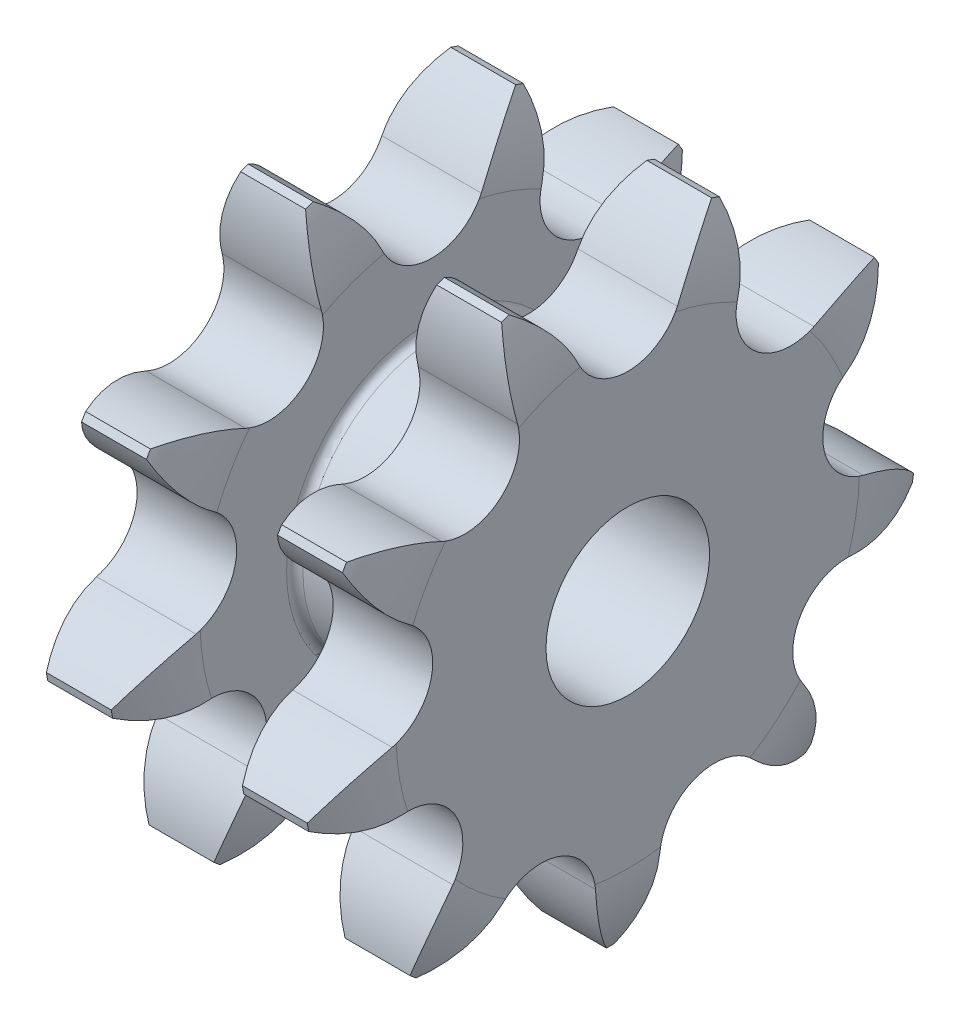
SolidWorks part; units mm, degrees
ref_plane "Plane1" through (0, 0, 0) normal (0, 0, 1) x (1, 0, 0)
ref_plane "Plane2" through (0, 0, 0) normal (0, 1, 0) x (1, 0, 0)
ref_plane "Plane3" through (0, 0, 0) normal (1, 0, 0) x (0, 0, -1)
sketch "Clipboard" plane through (0, 0, 0) normal (0, 1, 0) x (1, 0, 0)
  line L0 (0, 0) -> (12.5436, -1.9867)
  line L1 (-15, 0) -> (100, 0) construction
  line L2 (0, 0) -> (-0.8416, 0.9512)
  line L3 (0, 0) -> (-11.863, 4.5341)
  line L4 (0, 0) -> (3.0618, 0.4849)
  line L5 (0, 0) -> (-2.8109, -1.0484)
  line L6 (0, 0) -> (-17.9719, -12.1257)
  line L7 (-0.8416, 0.9512) -> (22.6002, 5.5078)
  line L8 (-76.2, 38.1) -> (-75.2, 38.1)
  line L9 (-73.4321, 41.7084) -> (-72.837, 41.7846)
  line L10 (-73.4741, 12.9512) -> (-59.0941, 12.9512)
  circle A0 centre (0, 0) radius 3.975
  circle A1 centre (0, 0) radius 10.0465
  circle A2 centre (0, 0) radius 25
  dimension "Num_teeth" = 9
  dimension "Thickness" = 21.68
  dimension "Fillet_rad" = 0.6
sketch "BasProSke" plane through (0, 0, 0) normal (0, 1, 0) x (1, 0, 0)
  line L0 (-10, 0) -> (60, 0) construction
  line L1 (0, 0) -> (0, 16.9929)
  line L2 (0, 0) -> (21.68, 0)
  line L3 (21.68, 0) -> (21.68, 16.9929)
  line L4 (20.41, 22.5287) -> (1.27, 22.5287)
  arc A0 (0, 16.9929) -> (1.27, 22.5287) centre (12.7, 16.9929) cw
  arc A1 (21.68, 16.9929) -> (20.41, 22.5287) centre (8.98, 16.9929) ccw
  dimension "D1" = 12.7
  dimension "Thickness" = 21.68
  dimension "Diameter" = 45.0573
  dimension "G1" = 1.27
revolve "Base-Revolve" add sketch "BasProSke" angle 360 about L0
sketch "GrvSke" plane through (0, 0, 0) normal (0, 1, 0) x (1, 0, 0)
  line L0 (7.3, 16.9929) -> (7.3, 10.6465)
  line L1 (7.9, 10.0465) -> (13.78, 10.0465)
  line L2 (14.38, 10.6465) -> (14.38, 16.9929)
  line L3 (6.03, 22.5287) -> (15.65, 22.5287)
  line L4 (10.84, 0) -> (10.84, 52.07) construction
  line L5 (-10, 0) -> (60, 0) construction
  line L6 (0, 0) -> (35.56, 0) construction
  arc A0 (14.38, 16.9929) -> (15.65, 22.5287) centre (27.08, 16.9929) cw
  arc A1 (7.3, 16.9929) -> (6.03, 22.5287) centre (-5.4, 16.9929) ccw
  arc A2 (7.3, 10.6465) -> (7.9, 10.0465) centre (7.9, 10.6465) ccw
  arc A3 (13.78, 10.0465) -> (14.38, 10.6465) centre (13.78, 10.6465) ccw
  dimension "D1" = 12.7
  dimension "Diameter" = 45.0573
  dimension "Fillet_rad" = 0.6
  dimension "G1" = 1.27
  dimension "Grv_width" = 7.08
revolve "Groove" cut sketch "GrvSke" angle 360 about L6
sketch "TooCutSke" plane through (0, 0, 0) normal (1, 0, 0) x (0, 0, -1)
  line L0 (0, 18.6059) -> (3.6386, 16.9092) construction
  line L1 (0, 0) -> (0, 107) construction
  line L2 (0, 18.6059) -> (-10, 18.6059) construction
  line L3 (0, 18.6059) -> (-3.6386, 16.9092) construction
  arc A0 (3.6386, 16.9092) -> (7.9748, 21.6037) centre (13.1494, 12.4742) cw
  arc A1 (3.6386, 16.9092) -> (-3.6386, 16.9092) centre (0, 18.6059) cw
  arc A2 (-3.6386, 16.9092) -> (-7.9748, 21.6037) centre (-13.1494, 12.4742) ccw
  arc A3 (7.9748, 21.6037) -> (-7.9748, 21.6037) centre (0, 0) ccw
extrude "ToothCut" cut sketch "TooCutSke" along normal through all
pattern_circular "TeethCuts" count 9 every 40 about axis through (-10, 0, 0) along (1, 0, 0) of "ToothCut"
sketch "HubNeaOneSke" plane through (0, 0, 0) normal (-1, 0, 0) x (0, 0, 1)
  circle A0 centre (0, 0) radius 10.0465
  dimension "Diameter" = 20.093
extrude "HubNearOne" [suppressed] add sketch "HubNeaOneSke" along normal blind 2.2005
fillet "HubNearOneFillet" [suppressed] radius 0.6
sketch "HubNeaBotSke" plane through (0, 0, 0) normal (-1, 0, 0) x (0, 0, 1)
  circle A0 centre (0, 0) radius 10.0465
  dimension "Diameter" = 20.093
extrude "HubNearBoth" [suppressed] add sketch "HubNeaBotSke" along normal blind 1.1003
fillet "HubNearBothFillet" [suppressed] radius 0.6
ref_plane "FarPln" through (21.68, 0, 0) normal (1, 0, 0) x (0, 0, -1)
sketch "HubFarSke" plane through (21.68, 0, 0) normal (1, 0, 0) x (0, 0, -1)
  circle A0 centre (0, 0) radius 10.0465
  dimension "Diameter" = 20.093
extrude "HubFar" [suppressed] add sketch "HubFarSke" along normal blind 1.1003
fillet "HubFarFillet" [suppressed] radius 0.6
sketch "BorSke" plane through (0, 0, 0) normal (1, 0, 0) x (0, 0, -1)
  circle A0 centre (0, 0) radius 6
  dimension "Diameter" = 12
extrude "Bore" cut sketch "BorSke" along normal mid plane 47.761
sketch "KeySke" plane through (0, 0, 0) normal (1, 0, 0) x (0, 0, -1)
  line L0 (-1, 0) -> (-1, 7)
  line L1 (-1, 7) -> (1, 7)
  line L2 (1, 7) -> (1, 0)
  line L3 (0, 0) -> (0, 34) construction
  line L4 (-1, 0) -> (1, 0)
  dimension "Offset" = 7
  dimension "Width" = 2
extrude "Keyway" [suppressed] cut sketch "KeySke" along normal mid plane 47.761
pattern_circular "Keyway2" [suppressed] count 2 every 90 about axis through (-10, 0, 0) along (1, 0, 0)
equation "' \"Pitch@Clipboard\" = 12.7"
equation "' \"Num_strands@Clipboard\" = 2"
equation "' \"Num_teeth@Clipboard\" = 9"
equation "' \"Hub_dia@Clipboard\" = 50"
equation "' \"Overall_len@Clipboard\" = 3"
equation "' \"Diameter@BorSke\" = 12"
equation "' \"T_dim@Clipboard\" = 1"
equation "' \"Width@KeySke\" = 2"
equation "' \"Dr@Clipboard\" = 7.95"
equation "' \"Face_width@Clipboard\" = 7.3"
equation "' \"Side_radius@Clipboard\" = 12.7"
equation "' \"Side_relief@Clipboard\" = 1.27"
equation "' \"Transv_pitch@Clipboard\" = 14.38"
equation "' \"Show_teeth@Clipboard\" = 9"
equation "' \"Fillet_rad@Clipboard\" = 0.6"
equation "' \"Plate_wid@Clipboard\" = 12"
equation "\"Num_teeth@Clipboard\" = int( \"Num_teeth@Clipboard\" )"
equation "\"Num_teeth@Clipboard\" = ((sgn( \"Num_teeth@Clipboard\" - 5.0)+1)*( \"Num_teeth@Clipboard\" - 5.0))/2 +5.0"
equation "\"Num_teeth@Clipboard\" = ((sgn( \"Num_teeth@Clipboard\" - 200.0)-1)*( \"Num_teeth@Clipboard\" - 200.0))/-2 +200.0"
equation "\"MHD@Clipboard\" = \"Pitch@Clipboard\" * (1.0 / tan(3.14159265 / \"Num_teeth@Clipboard\" )) - 1.05 * \"Plate_wid@Clipboard\" - 2.0 * \"Fillet_rad@Clipboard\" - 1.0"
equation "\"Thickness@Clipboard\"  = \"Face_width@Clipboard\" + (\"Num_strands@Clipboard\" - 1) * \"Transv_pitch@Clipboard\""
equation "\"OAL@Clipboard\" = \"Thickness@Clipboard\" + 2 * \"Fillet_rad@Clipboard\" + 1"
equation "\"MHD@Clipboard\" = ((sgn( \"MHD@Clipboard\" - \"Hub_dia@Clipboard\" )-1)*( \"MHD@Clipboard\" - \"Hub_dia@Clipboard\" ))/-2+ \"Hub_dia@Clipboard\""
equation "\"OAL@Clipboard\" = ((sgn( \"OAL@Clipboard\" - \"Overall_len@Clipboard\" )+1)*( \"OAL@Clipboard\" - \"Overall_len@Clipboard\" ))/2 + \"Overall_len@Clipboard\" + 0.0005"
equation "\"Num_teeth@TeethCuts\" = int( \"Show_teeth@Clipboard\" ) + 1"
equation "\"Num_teeth@TeethCuts\" = ((sgn( \"Num_teeth@TeethCuts\" - \"Num_teeth@Clipboard\" )-1)*( \"Num_teeth@TeethCuts\" - \"Num_teeth@Clipboard\" ))/-2+ \"Num_teeth@Clipboard\""
equation "\"Num_teeth@TeethCuts\" = ((sgn( \"Num_teeth@TeethCuts\" - 2.0)+1)*( \"Num_teeth@TeethCuts\" - 2.0))/2 +2.0"
equation "\"Angle@TeethCuts\" = 360.0 / \"Num_teeth@Clipboard\""
equation "\"Seat_radius@TooCutSke\" = ( \"Pitch@Clipboard\" / 2.0) / sin(3.14159265 / \"Num_teeth@Clipboard\" ) - \"Dr@Clipboard\" / 2.0 + \"Dr@Clipboard\" * 0.505"
equation "\"R1@TooCutSke\"  = \"Dr@Clipboard\" * 0.505"
equation "\"X@TooCutSke\" = 140.0 - (90.0 / \"Num_teeth@Clipboard\")"
equation "\"R2@TooCutSke\" = 0.12 * \"Dr@Clipboard\" * ( \"Num_teeth@Clipboard\" + 2.0)"
equation "\"Overcut@TooCutSke\" = 0.5 + 0.625 * \"Pitch@Clipboard\" - 0.5 * \"Dr@Clipboard\"  +  \"Pitch@Clipboard\" / 2.0 / sin(3.14159265 / \"Num_teeth@Clipboard\" )"
equation "\"Diameter@BasProSke\" = 2.0 * ( 0.625 * \"Pitch@Clipboard\" - 0.5 * \"Dr@Clipboard\"  +  \"Pitch@Clipboard\" / 2.0 / sin(3.14159265 / \"Num_teeth@Clipboard\" ))"
equation "\"Thickness@BasProSke\"  = \"Thickness@Clipboard\""
equation "\"G1@BasProSke\" =  \"Side_relief@Clipboard\""
equation "\"G2@BasProSke\" =  \"Side_relief@Clipboard\""
equation "\"D1@BasProSke\" =  \"Side_radius@Clipboard\""
equation "\"Diameter@GrvSke\" = \"Diameter@BasProSke\""
equation "\"G1@GrvSke\" = \"Side_relief@Clipboard\""
equation "\"D1@GrvSke\" = \"Side_radius@Clipboard\""
equation "\"Grv_diam@GrvSke\" =  \"Pitch@Clipboard\" * (1.0 / tan(3.14159265 / \"Num_teeth@Clipboard\" ))- 1.05 * \"Plate_wid@Clipboard\" - 2.0 * \"Fillet_rad@Clipboard\" - 1.0"
equation "\"Grv_width@GrvSke\" =  \"Transv_pitch@Clipboard\" - \"Face_width@Clipboard\""
equation "\"Offset@GrvSke\" = \"Grv_width@GrvSke\" / 2.0 + \"Face_width@Clipboard\""
equation "\"Fillet_rad@GrvSke\" = \"Fillet_rad@Clipboard\""
equation "\"Diameter@HubNeaOneSke\" = \"MHD@Clipboard\""
equation "\"Length@HubNearOne\" = \"OAL@Clipboard\" - \"Thickness@BasProSke\""
equation "\"Diameter@HubNeaBotSke\" = \"MHD@Clipboard\""
equation "\"Length@HubNearBoth\" = ( \"OAL@Clipboard\" - \"Thickness@BasProSke\" ) / 2.0"
equation "\"D1@HubNearOneFillet\" = \"Fillet_rad@Clipboard\""
equation "\"D1@HubNearBothFillet\" = \"Fillet_rad@Clipboard\""
equation "\"Thickness@FarPln\" = \"Thickness@BasProSke\""
equation "\"Diameter@HubFarSke\" = \"MHD@Clipboard\""
equation "\"Length@HubFar\" = ( \"OAL@Clipboard\" - \"Thickness@BasProSke\" ) / 2.0"
equation "\"D1@HubFarFillet\" = \"Fillet_rad@Clipboard\""
equation "\"D1@Bore\" = \"OAL@Clipboard\" * 2.0"
equation "\"D1@Keyway\" = \"OAL@Clipboard\" * 2.0"
equation "\"Offset@KeySke\" = \"T_dim@Clipboard\" + \"Diameter@BorSke\" / 2.0"
